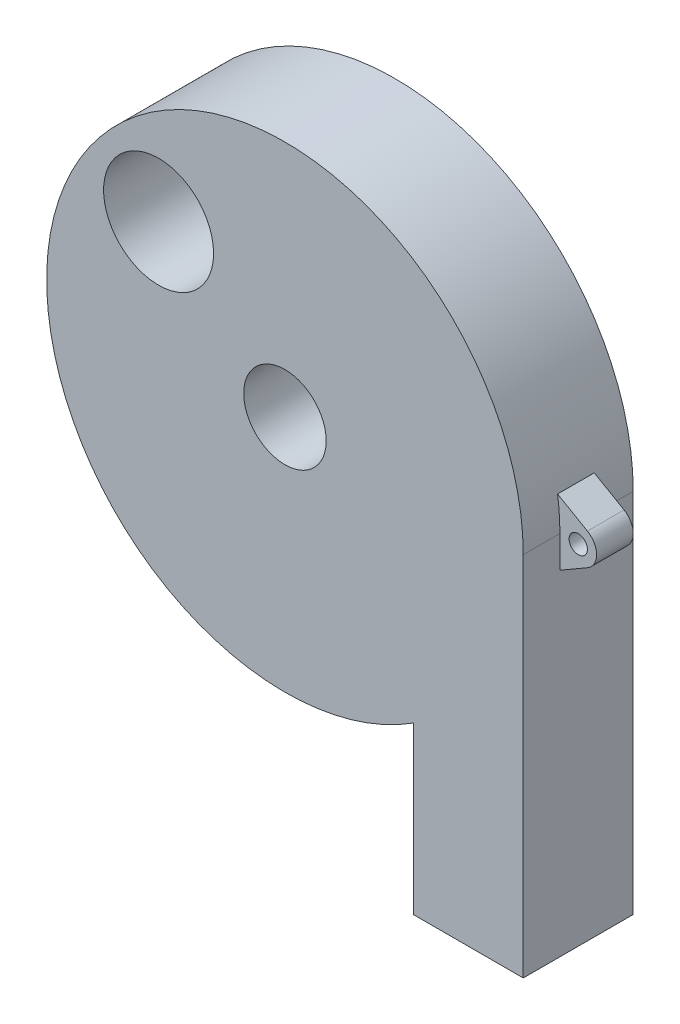
SolidWorks part; units mm, degrees
ref_plane "Front Plane" through (0, 0, 0) normal (0, 0, 1) x (1, 0, 0)
ref_plane "Top Plane" through (0, 0, 0) normal (0, 1, 0) x (1, 0, 0)
ref_plane "Right Plane" through (0, 0, 0) normal (1, 0, 0) x (0, 0, -1)
sketch "Sketch2" plane through (0, 0, 0) normal (0, 0, 1) x (1, 0, 0)
  line L0 (13, 0) -> (13, -20)
  line L1 (13, -20) -> (7, -20)
  line L2 (7, -20) -> (7, -10.9545)
  line L3 (10, 0) -> (10, -20) construction
  arc A0 (13, 0) -> (7, -10.9545) centre (0, 0) ccw
  circle A1 centre (0, 0) radius 10 construction
  dimension "Diameter" = 20
  dimension "Rod Holer Thickness" = 6
  dimension "Rod Holder Length" = 20
extrude "Boss-Extrude1" add sketch "Sketch2" along normal mid plane 6
hole_wizard "M4 Clearance Hole1" positions "Sketch3" profile "Sketch4" hole size "M4" standard "ANSI Metric" end condition up to next
sketch "Sketch3" plane through (0, 0, 3) normal (0, 0, 1) x (1, 0, 0)
  point P2 (0, 0)
sketch "Sketch4" plane through (0, 0, 3) normal (1, 0, 0) x (0, -1, 0)
  line L0 (0, 0) -> (0, 6)
  line L1 (0, 6) -> (2.25, 6)
  line L2 (2.25, 6) -> (2.25, 0)
  line L5 (2.25, 0) -> (0, 0)
  line L11 (0, -6.35) -> (0, 107.95) construction
  dimension "Thru Hole Dia." = 4.5
  dimension "Thru Hole Depth" = 6
sketch "Sketch5" plane through (0, -20, 0) normal (0, -1, 0) x (1, 0, 0)
  line L0 (13, 3) -> (7, -3) construction
  circle A0 centre (10, 0) radius 1.59
  dimension "Rod Hole Diameter" = 3.18
extrude "Cut-Extrude1" cut sketch "Sketch5" against normal blind 20
ref_axis "Axis1" through (10, 0, 0) along (0, -1, 0)
sketch "Sketch6" plane through (0, 0, 0) normal (0, 0, 1) x (1, 0, 0)
  line L0 (13, -20) -> (13, 0) construction
  line L1 (13, -1.7321) -> (13, 0)
  line L2 (13, -1.7321) -> (14.5, -0.866)
  line L3 (14.5, 0.866) -> (12.8741, 1.8047)
  arc A0 (13, 0) -> (7, -10.9545) centre (0, 0) ccw construction
  arc A1 (13, 0) -> (12.8741, 1.8047) centre (0, 0) ccw
  arc A2 (14.5, -0.866) -> (14.5, 0.866) centre (14, 0) ccw
  dimension "Spring Attchment Diameter" = 1
  dimension "D2" = 60
extrude "Boss-Extrude2" add sketch "Sketch6" along normal mid plane 2
sketch "Sketch7" plane through (0, 0, 1) normal (0, 0, 1) x (1, 0, 0)
  circle A0 centre (14, 0) radius 0.5
  arc A1 (14.5, -0.866) -> (14.5, 0.866) centre (14, 0) ccw construction
  dimension "Spring Hole Diam" = 1
extrude "Cut-Extrude2" cut sketch "Sketch7" against normal through all both and the other way through all
sketch "Sketch8" plane through (0, 0, 3) normal (0, 0, 1) x (1, 0, 0)
  line L0 (0, 0) -> (-21.8723, 0) construction
  line L1 (0, 0) -> (-6.8944, 5.7851) construction
  circle A0 centre (-6.8944, 5.7851) radius 3
  point P10 (-7.0859, 5.9458)
  point P11 (0, 0)
  dimension "D2" = 6
  dimension "D1" = 40
  dimension "D3" = 9
extrude "Cut-Extrude3" cut sketch "Sketch8" against normal through all
